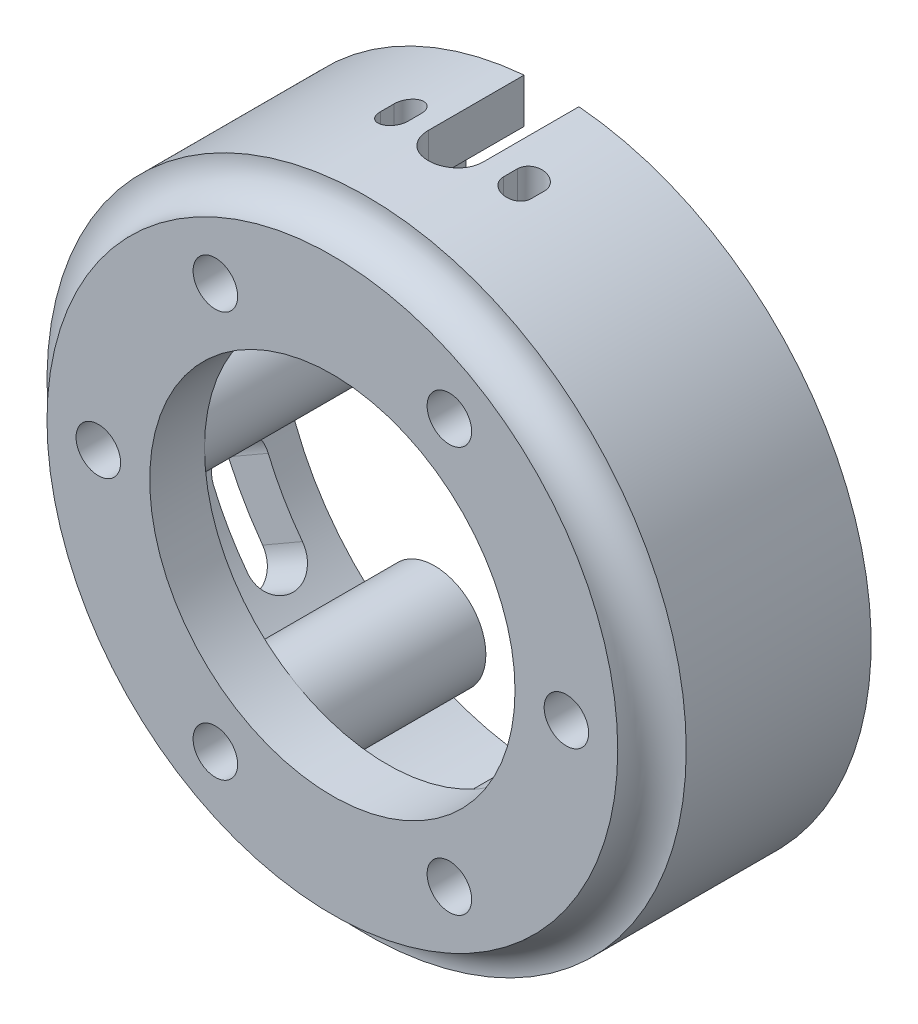
SolidWorks part; units mm, degrees
ref_plane "Front Plane" through (0, 0, 0) normal (0, 0, 1) x (1, 0, 0)
ref_plane "Top Plane" through (0, 0, 0) normal (0, 1, 0) x (1, 0, 0)
ref_plane "Right Plane" through (0, 0, 0) normal (1, 0, 0) x (0, 0, -1)
sketch "Sketch2" plane through (0, 0, 0) normal (0, 0, 1) x (1, 0, 0)
  circle A0 centre (0, 0) radius 13.335
  circle A1 centre (0, 0) radius 23.335
  dimension "D1" = 26.67
  dimension "D2" = 10
extrude "Boss-Extrude1" add sketch "Sketch2" along normal blind 3.5
ref_axis "Axis1" through (0, 0, 3.5) along (0, 0, -1)
sketch "Sketch3" plane through (0, 0, 0) normal (0, 1, 0) x (1, 0, 0)
  circle A1 centre (-23.335, -3.5) radius 2.5
  dimension "D1" = 5
revolve "Cut-Revolve1" cut sketch "Sketch3" angle 360 about axis through (0, 0, 3.5) along (0, 0, -1)
sketch "Sketch6" plane through (0, 0, 0) normal (0, 0, -1) x (-1, 0, 0)
  line L0 (0, 23.335) -> (0, 0) construction
  circle A0 centre (0, 0) radius 23.335 construction
  circle A1 centre (0, 0) radius 13.335
  circle A2 centre (0, 0) radius 23.335
  point P6 (0, 23.335)
  dimension "D2" = 10
extrude "Boss-Extrude2" add sketch "Sketch6" along normal blind 12.5
sketch "Sketch4" plane through (0, 0, 3.5) normal (0, 0, -1) x (-1, 0, 0)
  line L0 (13.335, 0) -> (20.835, 0) construction
  line L1 (17.085, 0) -> (8.5425, 14.796) construction
  line L2 (8.5425, 14.796) -> (-8.5425, 14.796) construction
  line L3 (-8.5425, 14.796) -> (-17.085, 0) construction
  line L4 (-17.085, 0) -> (-8.5425, -14.796) construction
  line L5 (-8.5425, -14.796) -> (8.5425, -14.796) construction
  line L6 (8.5425, -14.796) -> (17.085, 0) construction
  circle A0 centre (0, 0) radius 14.796 construction
  circle A1 centre (0, 0) radius 13.335 construction
  circle A2 centre (0, 0) radius 20.835 construction
  circle A3 centre (8.5425, 14.796) radius 1.625
  circle A4 centre (-8.5425, 14.796) radius 1.625
  circle A5 centre (-17.085, 0) radius 1.625
  circle A6 centre (-8.5425, -14.796) radius 1.625
  circle A7 centre (8.5425, -14.796) radius 1.625
  circle A8 centre (17.085, 0) radius 1.625
  dimension "D1" = 3.25
extrude "Cut-Extrude1" cut sketch "Sketch4" along normal through all
ref_plane "Plane2" through (0, 0, 0) normal (0, 1, 0) x (1, 0, 0)
sketch "Sketch10" plane through (0, 0, 0) normal (0, 1, 0) x (1, 0, 0)
  line L0 (0, 6.5) -> (0, 5.5) construction
  line L1 (-6.25, 0.5) -> (6.25, 0.5)
  line L2 (-6.25, 0.5) -> (-6.25, 11.5)
  line L3 (-6.25, 11.5) -> (6.25, 11.5)
  line L4 (6.25, 0.5) -> (6.25, 11.5)
  line L5 (-6.25, 0.5) -> (6.25, 11.5) construction
  line L6 (-6.25, 11.5) -> (6.25, 0.5) construction
  line L7 (2, 6.5) -> (2, 5.5)
  line L8 (-2, 6.5) -> (-2, 5.5)
  line L9 (-4.5, 6.5) -> (-4.5, 5.5) construction
  line L10 (-3.5, 6.5) -> (-3.5, 5.5)
  line L11 (-5.5, 6.5) -> (-5.5, 5.5)
  line L12 (4.5, 5.5) -> (4.5, 6.5) construction
  line L13 (3.5, 5.5) -> (3.5, 6.5)
  line L14 (5.5, 5.5) -> (5.5, 6.5)
  line L15 (23.335, -1) -> (-23.335, -1) construction
  line L16 (0, 11.5) -> (0, 0.5) construction
  arc A0 (2, 6.5) -> (-2, 6.5) centre (0, 6.5) ccw
  arc A1 (-2, 5.5) -> (2, 5.5) centre (0, 5.5) ccw
  arc A2 (-3.5, 6.5) -> (-5.5, 6.5) centre (-4.5, 6.5) ccw
  arc A3 (-5.5, 5.5) -> (-3.5, 5.5) centre (-4.5, 5.5) ccw
  arc A4 (3.5, 5.5) -> (5.5, 5.5) centre (4.5, 5.5) ccw
  arc A5 (5.5, 6.5) -> (3.5, 6.5) centre (4.5, 6.5) ccw
  point P0 (0, 6)
  point P8 (0, 6)
  point P15 (-4.5, 6)
  point P20 (4.5, 6)
  dimension "D3" = 2
  dimension "D5" = 1
  dimension "D1" = 12.5
  dimension "D2" = 11
  dimension "D4" = 1
  dimension "D6" = 9
  dimension "D7" = 6.5
extrude "Cut-Extrude3" cut sketch "Sketch10" along normal blind 20 contours L1 L4 L3 L2 A5 L14 A4 L13 A3 L11 A2 L10 A1 L8 A0 L7 | L14 A5 L13 A4 | L8 A1 L7 A0 | L11 A3 L10 A2 region at (-6.0835, 0, -6) region at (0, 0, -6) region at (-4.5, 0, -6) region at (4.5, 0, -6)
extrude "Cut-Extrude4" cut sketch "Sketch10<3>" along normal through all contours L14 A5 L13 A4 | L8 A1 L7 A0 | L11 A3 L10 A2 region at (0, 0, -6) region at (-4.5, 0, -6) region at (4.5, 0, -6)
sketch "Sketch10<3>" plane through (0, 0, 0) normal (0, 1, 0) x (1, 0, 0) same geometry as "Sketch10"
sketch "Sketch14" plane through (0, 0, 0) normal (0, 1, 0) x (1, 0, 0)
  line L0 (23.335, 12.5) -> (-23.335, 12.5) construction
  line L1 (-6.25, 11.5) -> (6.25, 11.5)
  line L2 (-6.25, 11.5) -> (-6.25, 12.5)
  line L3 (-6.25, 12.5) -> (6.25, 12.5)
  line L4 (6.25, 11.5) -> (6.25, 12.5)
  line L5 (6.25, 0.5) -> (6.25, 11.5) construction
extrude "Cut-Extrude7" cut sketch "Sketch14" against normal up to surface (-20 mm away) up to face at (-4.5, 20, -6)
sketch "Sketch16" plane through (0, 20, 0) normal (0, -1, 0) x (1, 0, 0)
  line L0 (-6.25, -12.5) -> (6.25, -12.5) construction
  line L1 (2, -6.5) -> (-2, -6.5)
  line L2 (2, -6.5) -> (2, -12.5)
  line L3 (2, -12.5) -> (-2, -12.5)
  line L4 (-2, -6.5) -> (-2, -12.5)
  line L5 (-2, -5.5) -> (-2, -6.5) construction
extrude "Cut-Extrude9" cut sketch "Sketch16" against normal through all
ref_plane "Plane3" through (0, 0, 0) normal (0.866, 0.5, 0) x (0, 0, -1)
sketch "Sketch17" plane through (0, 0, 0) normal (-0.866, -0.5, 0) x (0, 0, -1)
  line L0 (8.25, 2.5) -> (8.25, -2.5) construction
  line L1 (10.25, 2.5) -> (10.25, -2.5)
  line L2 (6.25, 2.5) -> (6.25, -2.5)
  line L4 (12.5, -23.335) -> (4, -23.335) construction
  line L7 (12.5, -23.335) -> (12.5, 23.335) construction
  line L8 (-3.5, 0) -> (0, 0) construction
  arc A0 (10.25, 2.5) -> (6.25, 2.5) centre (8.25, 2.5) ccw
  arc A1 (6.25, -2.5) -> (10.25, -2.5) centre (8.25, -2.5) ccw
  point P2 (8.25, 0)
  point P12 (8.25, -23.335)
  point P15 (8.25, -23.335)
  dimension "D2" = 2
  dimension "D1" = 5
  dimension "D3" = 8.5
extrude "Cut-Extrude10" cut sketch "Sketch17" along normal through all
sketch "Sketch18" plane through (0, 0, -12.5) normal (0, 0, -1) x (-1, 0, 0)
  line L0 (6.25, 20) -> (-6.25, 20) construction
  line L1 (-6.25, 11.7796) -> (-6.25, 18.9984)
  line L2 (-6.25, 20) -> (-6.25, 11.7796) construction
  line L3 (6.25, 18.9984) -> (6.25, 11.7796)
  line L4 (6.25, 20) -> (6.25, 11.7796) construction
  arc A0 (-12.1771, 15.8656) -> (-19.8371, 2.5472) centre (0, 0) ccw
  arc A1 (-12.1771, 15.8656) -> (-6.25, 11.7796) centre (-8.5425, 14.796) ccw
  arc A2 (-19.8371, -2.5472) -> (-19.8371, 2.5472) centre (-17.085, 0) ccw
  arc A3 (-7.7126, -18.4531) -> (-12.1245, -15.9059) centre (-8.5425, -14.796) ccw
  arc A4 (12.1245, -15.9059) -> (7.7126, -18.4531) centre (8.5425, -14.796) ccw
  arc A5 (19.8371, 2.5472) -> (19.8371, -2.5472) centre (17.085, 0) ccw
  arc A7 (-6.25, 11.7796) -> (6.25, 11.7796) centre (0, 0) ccw construction
  arc A8 (6.25, 18.9984) -> (-6.25, 18.9984) centre (0, 0) ccw
  arc A9 (19.8371, 2.5472) -> (12.1771, 15.8656) centre (0, 0) ccw
  arc A10 (12.1245, -15.9059) -> (19.8371, -2.5472) centre (0, 0) ccw
  arc A11 (-7.7126, -18.4531) -> (7.7126, -18.4531) centre (0, 0) ccw
  arc A12 (-19.8371, -2.5472) -> (-12.1245, -15.9059) centre (0, 0) ccw
  arc A14 (6.25, 11.7796) -> (12.1771, 15.8656) centre (8.5425, 14.796) ccw
extrude "Cut-Extrude11" cut sketch "Sketch18" against normal up to surface (12 mm away) up to face at (0, 16.2787, -0.5)
